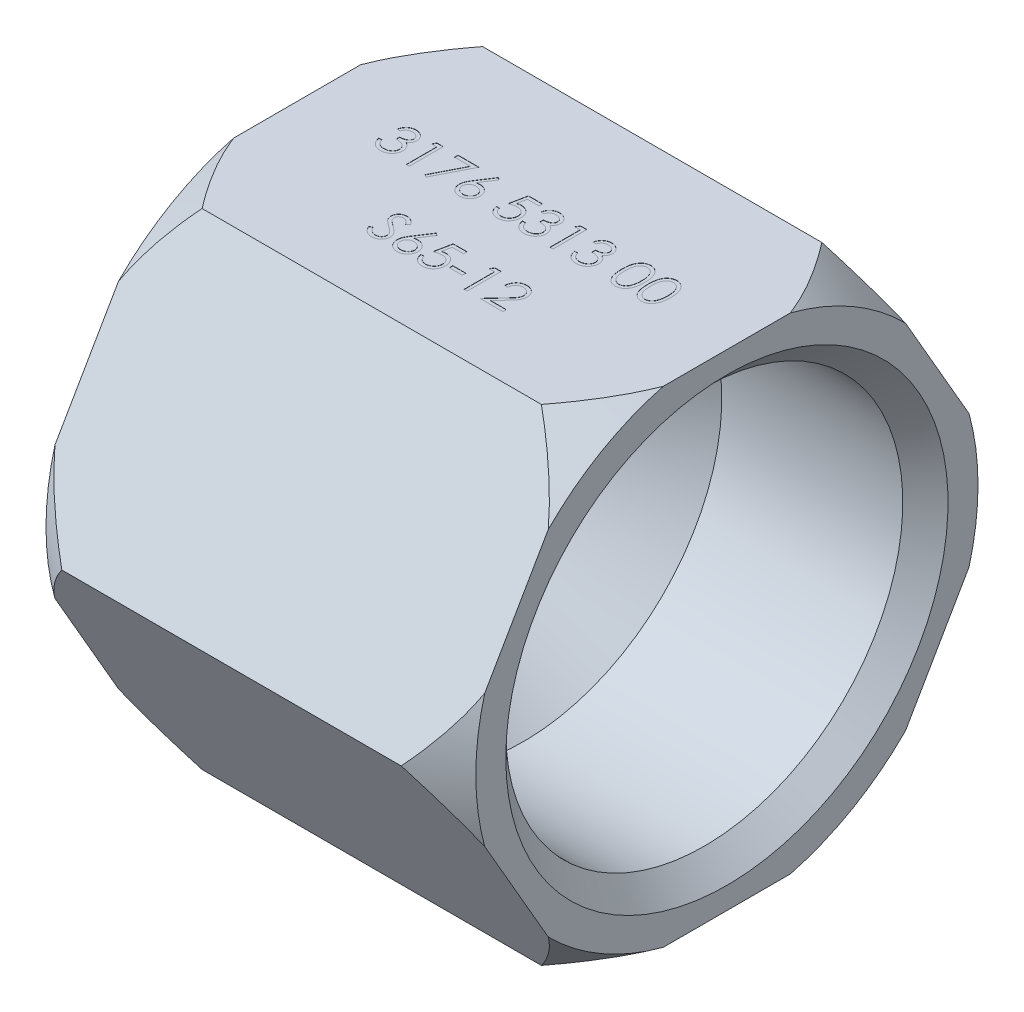
SolidWorks part; units mm, degrees
material "C1020"
ref_plane "Front Plane" through (0, 0, 0) normal (0, 0, 1) x (1, 0, 0)
ref_plane "Top Plane" through (0, 0, 0) normal (0, 1, 0) x (1, 0, 0)
ref_plane "Right Plane" through (0, 0, 0) normal (1, 0, 0) x (0, 0, -1)
sketch "Sketch1" plane through (0, 0, 0) normal (0, 0, 1) x (1, 0, 0)
  line L0 (0, 0) -> (32.0688, 0) construction
  line L1 (0, 0) -> (0, 11.1)
  line L2 (0, 11.1) -> (2, 12.4)
  line L3 (2, 12.4) -> (17, 12.4)
  line L4 (17, 12.4) -> (19, 11.1)
  line L5 (19, 11.1) -> (19, 8.775)
  line L6 (19, 8.775) -> (10, 8.775)
  line L7 (10, 8.775) -> (3, 3.5001)
  line L9 (0, 0) -> (3, 0)
  line L11 (3, 3.5001) -> (3, 0)
  dimension "D1" = 16
  dimension "D2" = 37
  dimension "D3" = 19
  dimension "D4" = 22.2
  dimension "D5" = 24.8
  dimension "D7" = 2
  dimension "D6" = 2
  dimension "D8" = 17.55
  dimension "D9" = 9
revolve "Revolve1" add sketch "Sketch1" angle 360 about L0
sketch "Sketch2" plane through (19, 0, 0) normal (1, 0, 0) x (0, 0, -1)
  line L1 (6.2, 10.7387) -> (-6.2, 10.7387)
  line L2 (-6.2, 10.7387) -> (-12.4, 0)
  line L3 (-12.4, 0) -> (-6.2, -10.7387)
  line L4 (-6.2, -10.7387) -> (6.2, -10.7387)
  line L5 (6.2, -10.7387) -> (12.4, 0)
  line L6 (12.4, 0) -> (6.2, 10.7387)
  circle A0 centre (0, 0) radius 10.7387 construction
  circle A1 centre (0, 0) radius 12.4 construction
extrude "Extrude1" cut sketch "Sketch2" against normal up to surface (19 mm away) flip side to cut up to face at (0, 0, 11.1)
chamfer "Chamfer1" distance 1 angle 45 1 edges at (19, 0, 8.775)
sketch "Sketch3" plane through (0, 10.7387, 0) normal (0, 1, 0) x (1, 0, 0)
  line L0 (0, 0) -> (19, 0) construction
  line L1 (19, -2.8089) -> (19, 2.8089) construction
  text T0 "3176 5313 00\r\nS65-12" font "Century Gothic" height 1.5
extrude "Cut-Extrude1" cut sketch "Sketch3" against normal blind 0.01
